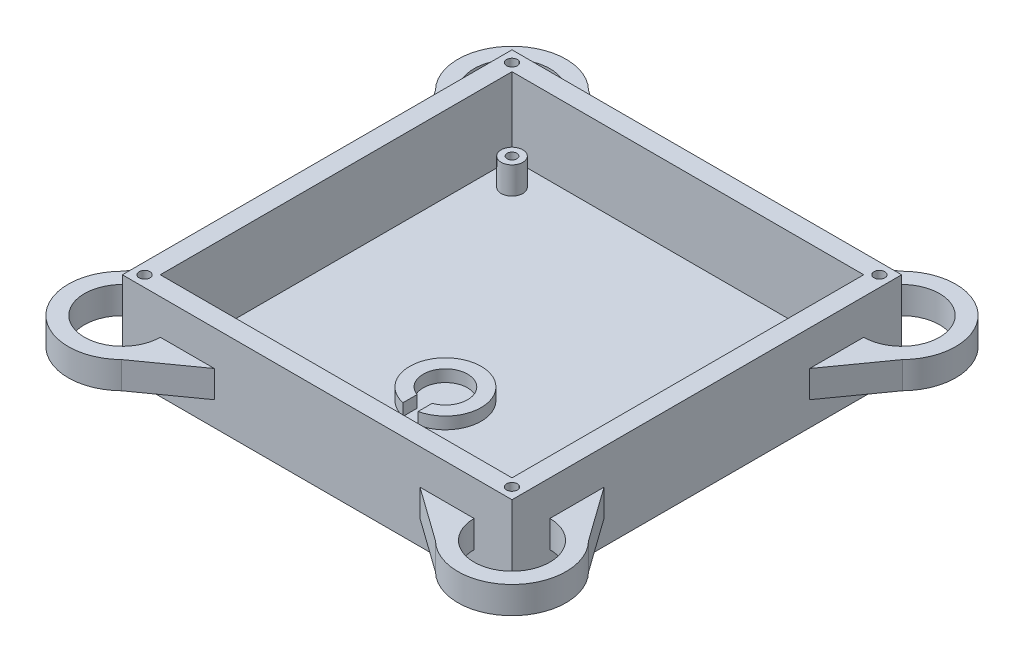
SolidWorks part; units mm, degrees
ref_plane "Front Plane" through (0, 0, 0) normal (0, 0, 1) x (1, 0, 0)
ref_plane "Top Plane" through (0, 0, 0) normal (0, 1, 0) x (1, 0, 0)
ref_plane "Right Plane" through (0, 0, 0) normal (1, 0, 0) x (0, 0, -1)
sketch "Sketch1" plane through (0, 0, 0) normal (0, 1, 0) x (1, 0, 0)
  line L2 (-35, 31) -> (30, 31)
  line L3 (30, 31) -> (30, -34)
  line L5 (-35, -34) -> (30, -34)
  line L6 (-35, 31) -> (-35, -34)
  line L7 (-1, 34.5) -> (33.5, 34.5)
  line L8 (33.5, 34.5) -> (-38.5, 34.5)
  line L9 (-38.5, 34.5) -> (-38.5, -37.5)
  line L11 (33.5, 34.5) -> (33.5, -37.5)
  line L12 (33.5, -37.5) -> (-38.5, -37.5)
  line L13 (0, -34) -> (0, -53.1946) construction
  dimension "D1" = 65
  dimension "D2" = 3.5
  dimension "D3" = 3.5
  dimension "D4" = 65
  dimension "D5" = 3.5
  dimension "D6" = 3.5
extrude "Boss-Extrude1" add sketch "Sketch1" along normal blind 14 contours L6 L2 L3 L5 L12 L11 L7 L8 L9 region at (16.25, 0, -33.4818)
sketch "Sketch2" plane through (0, 0, 0) normal (0, -1, 0) x (1, 0, 0)
  line L1 (-38.5, 37.5) -> (33.5, 37.5)
  line L2 (-38.5, 37.5) -> (-38.5, -34.5)
  line L3 (-38.5, -34.5) -> (33.5, -34.5)
  line L4 (33.5, 37.5) -> (33.5, -34.5)
extrude "Boss-Extrude2" add sketch "Sketch2" along normal blind 2
sketch "Sketch3" plane through (0, 0, 0) normal (0, 1, 0) x (1, 0, 0)
  line L0 (-2.5, 31) -> (-2.5, -34) construction
  line L1 (-35, 31) -> (30, 31) construction
  line L2 (-35, -34) -> (30, -34) construction
  line L3 (-2.5, -34) -> (-2.5, -1.5) construction
  line L4 (-2.5, -1.5) -> (30, -1.5) construction
  line L5 (30, 31) -> (30, -34) construction
  line L6 (30, -1.5) -> (-35, -1.5) construction
  line L7 (-35, 31) -> (-35, -34) construction
  line L8 (-32.5, 28.5) -> (27.5, 28.5) construction
  line L9 (27.5, 28.5) -> (27.5, -31.5) construction
  line L10 (-32.5, -31.5) -> (27.5, -31.5) construction
  line L11 (-32.5, 28.5) -> (-32.5, -31.5) construction
  circle A0 centre (25.5, 26.5) radius 2
  circle A1 centre (25.5, 26.5) radius 0.9
  circle A2 centre (25.5, -29.5) radius 2
  circle A3 centre (25.5, -29.5) radius 0.9
  circle A4 centre (-30.5, -29.5) radius 0.9
  circle A5 centre (-30.5, -29.5) radius 2
  circle A6 centre (-30.5, 26.5) radius 2
  circle A7 centre (-30.5, 26.5) radius 0.9
  point P23 (27.5, -1.5)
  point P28 (-2.5, -31.5)
  point P32 (-2.5, 28.5)
  dimension "D3" = 2
  dimension "D4" = 4
  dimension "D5" = 2
  dimension "D1" = 30
  dimension "D2" = 30
extrude "Boss-Extrude3" add sketch "Sketch3" along normal blind 5
sketch "Sketch4" plane through (0, 14, 0) normal (0, 1, 0) x (1, 0, 0)
  line L0 (-2.5, 34.5) -> (-2.5, -37.5) construction
  line L1 (-38.5, 34.5) -> (33.5, 34.5) construction
  line L2 (33.5, -37.5) -> (-38.5, -37.5) construction
  line L3 (-38.5, -1.5) -> (33.5, -1.5) construction
  line L5 (-38.5, 34.5) -> (-38.5, -37.5) construction
  line L7 (-35, 31) -> (-38.5, 34.5) construction
  line L9 (33.5, 34.5) -> (33.5, -37.5) construction
  circle A1 centre (-36.4494, 32.4494) radius 1
  circle A2 centre (31.4494, 32.4494) radius 1
  circle A3 centre (31.4494, -35.4494) radius 1
  circle A4 centre (-36.4494, -35.4494) radius 1
  dimension "D1" = 2.9
extrude "Cut-Extrude1" cut sketch "Sketch4" against normal blind 8
ref_plane "Plane1" through (0, 5, 0) normal (0, -1, 0) x (-1, 0, 0)
sketch "Sketch5" plane through (0, 5, 0) normal (0, 1, 0) x (1, 0, 0)
  line L0 (33.5, 34.5) -> (26.5, 41.1203) construction
  line L1 (33.5, 34.5) -> (26.5, 34.5)
  line L2 (26.5, 34.5) -> (26.5, 41.6414) construction
  line L3 (26.5, 34.5) -> (33.5, 34.5)
  line L5 (33.5, 34.5) -> (33.5, -37.5) construction
  line L6 (26.5, 34.5) -> (23.5, 34.5)
  line L7 (26.5, 41.6414) -> (26.5, 27.5) construction
  line L8 (33.5, 27.5) -> (33.5, 24.5)
  line L9 (-2.5, 38.4614) -> (-2.5, -44.4375) construction
  line L10 (-42.2092, -1.5) -> (36.5358, -1.5) construction
  line L14 (-31.5, 34.5) -> (-28.5, 34.5)
  line L19 (-38.5, 34.5) -> (33.5, 34.5) construction
  line L20 (26.5, 27.5) -> (40.6414, 27.5) construction
  line L21 (26.5, 41.6414) -> (16.5, 34.5)
  line L22 (16.5, 34.5) -> (23.5, 34.5)
  line L23 (40.6414, 27.5) -> (33.5, 17.5)
  line L24 (33.5, 17.5) -> (33.5, 24.5)
  line L25 (-21.5, 34.5) -> (-28.5, 34.5)
  line L26 (-31.5, 41.6414) -> (-21.5, 34.5)
  line L27 (-45.6414, 27.5) -> (-38.5, 17.5)
  line L28 (-38.5, 17.5) -> (-38.5, 24.5)
  line L29 (-38.5, 27.5) -> (-38.5, 24.5)
  line L30 (26.5, -37.5) -> (23.5, -37.5)
  line L31 (16.5, -37.5) -> (23.5, -37.5)
  line L32 (26.5, -44.6414) -> (16.5, -37.5)
  line L33 (40.6414, -30.5) -> (33.5, -20.5)
  line L34 (33.5, -20.5) -> (33.5, -27.5)
  line L35 (33.5, -30.5) -> (33.5, -27.5)
  line L36 (-38.5, -30.5) -> (-38.5, -27.5)
  line L37 (-38.5, -20.5) -> (-38.5, -27.5)
  line L38 (-45.6414, -30.5) -> (-38.5, -20.5)
  line L39 (-31.5, -44.6414) -> (-21.5, -37.5)
  line L40 (-21.5, -37.5) -> (-28.5, -37.5)
  line L41 (-31.5, -37.5) -> (-28.5, -37.5)
  arc A0 (33.5, 27.5) -> (26.5, 34.5) centre (33.5, 34.5) ccw
  arc A1 (40.6414, 27.5) -> (26.5, 41.6414) centre (33.5, 34.5) ccw
  arc A8 (-45.6414, 27.5) -> (-31.5, 41.6414) centre (-38.5, 34.5) cw
  arc A9 (-38.5, 27.5) -> (-31.5, 34.5) centre (-38.5, 34.5) cw
  arc A10 (40.6414, -30.5) -> (26.5, -44.6414) centre (33.5, -37.5) cw
  arc A11 (33.5, -30.5) -> (26.5, -37.5) centre (33.5, -37.5) cw
  arc A12 (-38.5, -30.5) -> (-31.5, -37.5) centre (-38.5, -37.5) ccw
  arc A13 (-45.6414, -30.5) -> (-31.5, -44.6414) centre (-38.5, -37.5) ccw
  dimension "D3" = 7
  dimension "D2" = 7
extrude "Boss-Extrude6" add sketch "Sketch5" along normal blind 2.5 and the other way blind 2.5 contours A9 L29 L28 L27 A8 L26 L25 L14 | A13 L38 L37 L36 A12 L41 L40 L39 | A1 L23 L24 L8 A0 L6 L22 L21 | A11 L35 L34 L33 A10 L32 L31 L30 region at (25, 5, -34.8818) region at (-43.7197, 5, -39.7197) region at (38.7197, 5, 42.7197) region at (-43.7197, 5, 42.7197)
sketch "Sketch10" plane through (0, 0, 0) normal (0, 1, 0) x (1, 0, 0)
  line L0 (-2.5, 31) -> (-2.5, -9.7) construction
  line L1 (-35, 31) -> (30, 31) construction
  line L4 (-35, 31) -> (-35, -34) construction
  line L5 (-35, -1.5) -> (30, -1.5) construction
  line L6 (30, 31) -> (30, -34) construction
  line L13 (-3.9, -17.6536) -> (-3.9, -20.2498)
  line L14 (-1.1, -17.6536) -> (-1.1, -20.2498)
  arc A0 (-1.1, -17.6536) -> (-3.9, -17.6536) centre (-2.5, -13.8) ccw
  arc A1 (-1.1, -20.2498) -> (-3.9, -20.2498) centre (-2.5, -13.8) ccw
  dimension "D2" = 8.2
  dimension "D1" = 13.2
extrude "Boss-Extrude7" add sketch "Sketch10" along normal blind 2.2
